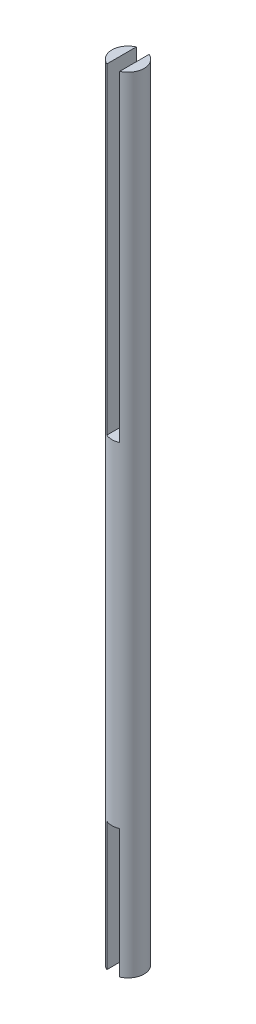
SolidWorks part; units mm, degrees
ref_plane "Front Plane" through (0, 0, 0) normal (0, 0, 1) x (1, 0, 0)
ref_plane "Top Plane" through (0, 0, 0) normal (0, 1, 0) x (1, 0, 0)
ref_plane "Right Plane" through (0, 0, 0) normal (1, 0, 0) x (0, 0, -1)
sketch "Sketch1" plane through (0, 0, 0) normal (0, 1, 0) x (1, 0, 0)
  circle A0 centre (0, 0) radius 5
  dimension "D1" = 10
extrude "Boss-Extrude1" add sketch "Sketch1" along normal blind 104
sketch "Sketch2" plane through (0, 104, 0) normal (0, 1, 0) x (1, 0, 0)
  line L0 (0, 0) -> (0, 5.3588) construction
  line L1 (-2, 4.5826) -> (-2, -4.5826)
  line L2 (2, 4.5826) -> (2, -4.5826)
  circle A0 centre (0, 0) radius 5 construction
  arc A1 (-2, 4.5826) -> (-2, -4.5826) centre (0, 0) ccw
  arc A2 (2, -4.5826) -> (2, 4.5826) centre (0, 0) ccw
  dimension "D1" = 4
extrude "Boss-Extrude2" add sketch "Sketch2" along normal blind 100
extrude "Boss-Extrude3" add sketch "Sketch2<2>" against normal blind 40 from surface starting at face at (0, 0, 5)
sketch "Sketch2<2>" plane through (0, 104, 0) normal (0, 1, 0) x (1, 0, 0) same geometry as "Sketch2"
